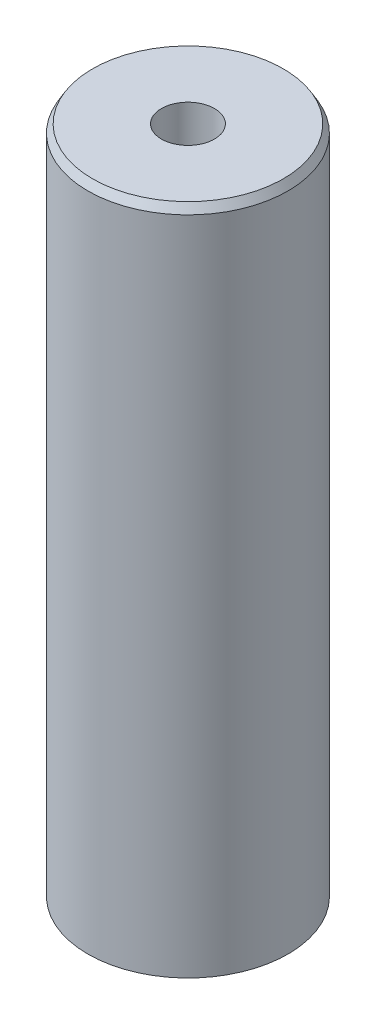
SolidWorks part; units mm, degrees
ref_plane "Front Plane" through (0, 0, 0) normal (0, 0, 1) x (1, 0, 0)
ref_plane "Top Plane" through (0, 0, 0) normal (0, 1, 0) x (1, 0, 0)
ref_plane "Right Plane" through (0, 0, 0) normal (1, 0, 0) x (0, 0, -1)
sketch "Sketch1" plane through (0, 0, 0) normal (0, 1, 0) x (1, 0, 0)
  circle A0 centre (0, 0) radius 12.5
  dimension "SHAFT_OD" = 25
extrude "Boss-Extrude1" add sketch "Sketch1" along normal blind 84.1664
sketch "Sketch2" plane through (0, 0, 0) normal (0, 1, 0) x (1, 0, 0)
  circle A0 centre (0, 0) radius 3.3121
  dimension "BORE_D" = 6.6243
extrude "Cut-Extrude1" cut sketch "Sketch2" along normal through all
chamfer "Chamfer1" distance 1.0171 angle 30 2 edges at (0, 84.1664, 12.5) (0, 0, 12.5) first distance on face at (0, 84.1664, 12.5) first distance on face at (0, 0, 3.3121)
